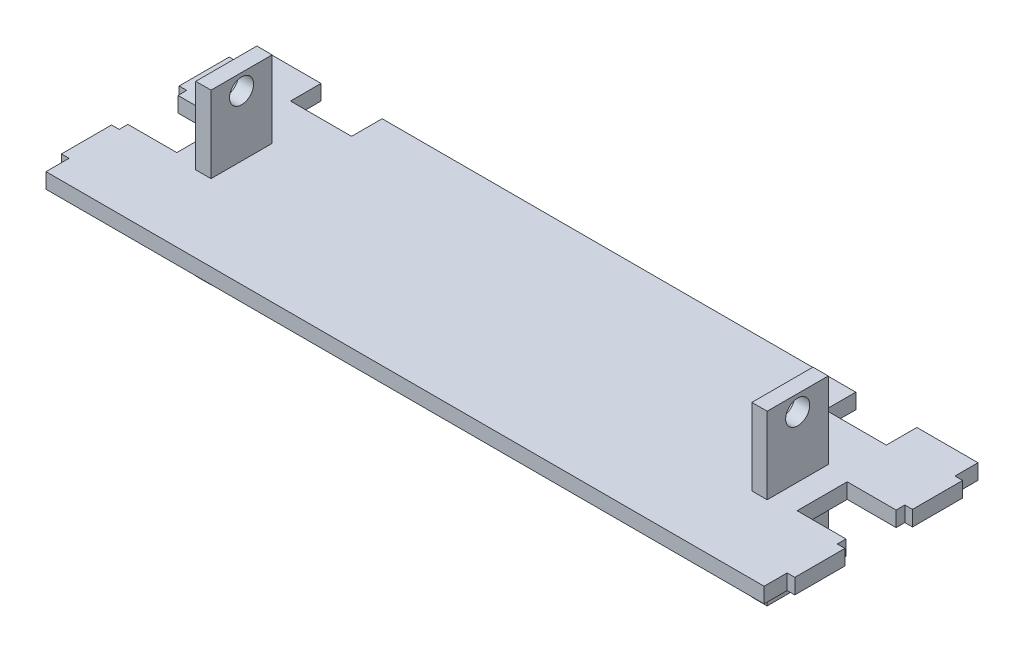
SolidWorks part; units mm, degrees
ref_plane "Front Plane" through (0, 0, 0) normal (0, 0, 1) x (1, 0, 0)
ref_plane "Top Plane" through (0, 0, 0) normal (0, 1, 0) x (1, 0, 0)
ref_plane "Right Plane" through (0, 0, 0) normal (1, 0, 0) x (0, 0, -1)
sketch "Sketch1" plane through (0, 0, 0) normal (0, 1, 0) x (1, 0, 0)
  line L0 (0, 72.39) -> (0, -44.45) construction
  line L1 (149.225, -44.45) -> (-149.225, -44.45)
  line L2 (149.225, -44.45) -> (149.225, -34.8747)
  line L3 (149.225, 44.45) -> (123.825, 44.45)
  line L4 (-149.225, -44.45) -> (-149.225, -34.8747)
  line L5 (149.225, -44.45) -> (-149.225, 44.45) construction
  line L6 (149.225, 44.45) -> (-149.225, -44.45) construction
  line L7 (149.225, 10.414) -> (128.905, 10.414)
  line L9 (149.225, -10.414) -> (128.905, -10.414)
  line L10 (128.905, 10.414) -> (128.905, -10.414)
  line L11 (-123.825, 44.45) -> (-149.225, 44.45)
  line L13 (-149.225, -10.414) -> (-128.905, -10.414)
  line L14 (-128.905, 10.414) -> (-128.905, -10.414)
  line L15 (-149.225, 10.414) -> (-128.905, 10.414)
  line L17 (-127, 0) -> (127, 0) construction
  line L18 (-149.225, 14.0467) -> (-152.4, 14.0467)
  line L20 (-149.225, 34.8747) -> (-152.4, 34.8747)
  line L21 (-152.4, 14.0467) -> (-152.4, 34.8747)
  line L22 (-149.225, -34.8747) -> (-152.4, -34.8747)
  line L23 (-152.4, -14.0467) -> (-152.4, -34.8747)
  line L24 (-149.225, -14.0467) -> (-152.4, -14.0467)
  line L27 (149.225, -14.0467) -> (152.4, -14.0467)
  line L28 (152.4, -14.0467) -> (152.4, -34.8747)
  line L29 (149.225, -34.8747) -> (152.4, -34.8747)
  line L30 (149.225, 34.8747) -> (152.4, 34.8747)
  line L31 (152.4, 14.0467) -> (152.4, 34.8747)
  line L32 (149.225, 14.0467) -> (152.4, 14.0467)
  line L34 (-149.225, 34.8747) -> (-149.225, 44.45)
  line L35 (-149.225, -14.0467) -> (-149.225, -10.414)
  line L36 (149.225, 34.8747) -> (149.225, 44.45)
  line L37 (149.225, -14.0467) -> (149.225, -10.414)
  line L38 (-149.225, 10.414) -> (-149.225, 14.0467)
  line L39 (149.225, 10.414) -> (149.225, 14.0467)
  line L40 (-123.825, 44.45) -> (-123.825, 31.75)
  line L41 (-123.825, 31.75) -> (-98.425, 31.75)
  line L42 (-98.425, 44.45) -> (-98.425, 31.75)
  line L44 (98.425, 44.45) -> (98.425, 31.75)
  line L45 (98.425, 31.75) -> (123.825, 31.75)
  line L46 (123.825, 44.45) -> (123.825, 31.75)
  line L47 (98.425, 44.45) -> (-98.425, 44.45)
  point P0 (0, 0)
  point P6 (127, 0)
  dimension "D1" = 298.45
  dimension "D2" = 88.9
  dimension "D3" = 20.828
  dimension "D5" = 3.175
  dimension "D6" = 20.828
  dimension "D4" = 20.32
  dimension "D7" = 12.7
  dimension "D8" = 25.4
  dimension "D9" = 25.4
  dimension "D10" = 12.7
  dimension "D12" = 25.4
  dimension "D11" = 25.4
  dimension "D13" = 304.8
extrude "Boss-Extrude1" add sketch "Sketch1" along normal mid plane 6.35
sketch "Sketch2" plane through (0, 0, 0) normal (0, 1, 0) x (1, 0, 0)
  line L1 (112.395, -12.7) -> (118.745, -12.7)
  line L2 (112.395, -12.7) -> (112.395, 12.7)
  line L3 (112.395, 12.7) -> (118.745, 12.7)
  line L4 (118.745, -12.7) -> (118.745, 12.7)
  line L5 (112.395, -12.7) -> (118.745, 12.7) construction
  line L6 (112.395, 12.7) -> (118.745, -12.7) construction
  line L7 (0, 44.45) -> (0, -44.45) construction
  line L8 (98.425, 44.45) -> (-98.425, 44.45) construction
  line L13 (128.905, -10.414) -> (128.905, 10.414) construction
  line L14 (-149.225, -44.45) -> (149.225, -44.45) construction
  line L15 (-112.395, -12.7) -> (-112.395, 12.7)
  line L16 (-112.395, -12.7) -> (-118.745, -12.7)
  line L17 (-118.745, -12.7) -> (-118.745, 12.7)
  line L18 (-112.395, 12.7) -> (-118.745, 12.7)
  point P0 (115.57, 0)
  point P10 (128.905, 0)
  dimension "D2" = 10.16
  dimension "D4" = 25.4
  dimension "D5" = 6.35
extrude "Boss-Extrude2" add sketch "Sketch2" along normal mid plane 70.104
sketch "Sketch5" plane through (-118.745, 0, 0) normal (-1, 0, 0) x (0, 0, 1)
  line L1 (-44.45, 0) -> (44.45, 0) construction
  line L2 (-44.45, 3.175) -> (-44.45, -3.175) construction
  line L3 (44.45, 3.175) -> (44.45, -3.175) construction
  circle A0 centre (0, 28.448) radius 5.0038
  circle A1 centre (0, -28.448) radius 5.0038
  dimension "D2" = 10.0076
extrude "Cut-Extrude1" cut sketch "Sketch5" against normal through all both and the other way through all
equation "\"length\" = \"Avionics_Board_Length\""
equation "\"width\"=3.5"
equation "\"height\"= 0.25"
equation "\"D2@Sketch1\"=\"width\""
equation "\"eyebolt width\"= 0.82"
equation "\"eyebolt length\"= 0.8"
equation "\"D3@Sketch1\"=\"eyebolt width\""
equation "\"D4@Sketch1\"=\"eyebolt length\""
equation "\"lead screw holder height\"= 2.76"
equation "\"lead screw diameter\"=0.394"
equation "\"distance from holders to board\"=0.4"
equation "\"D2@Sketch5\"=\"lead screw diameter\""
equation "\"Mid_Coupler_Length\" = 12in"
equation "\"Avionics_Bulkhead_Thickness\" = 0.25in"
equation "\"Avionics_Bulkhead_Lip\" = 0.125in"
equation "\"Avionics_Board_Length\" = \"Mid_Coupler_Length\" - 2*\"Avionics_Bulkhead_Lip\""
equation "\"Body_Tube_OD\"= 4.024in"
equation "\"D1@Sketch1\"=\"length\""
